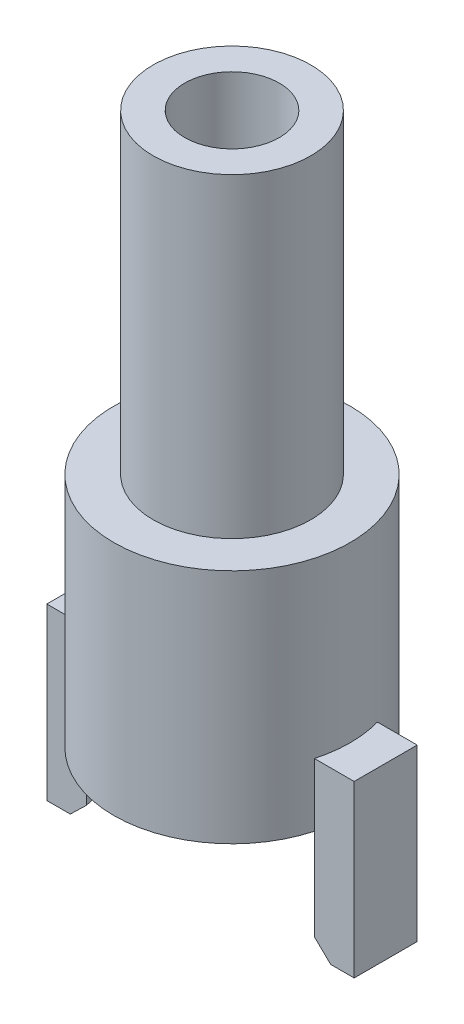
SolidWorks part; units mm, degrees
ref_plane "Front Plane" through (0, 0, 0) normal (0, 0, 1) x (1, 0, 0)
ref_plane "Top Plane" through (0, 0, 0) normal (0, 1, 0) x (1, 0, 0)
ref_plane "Right Plane" through (0, 0, 0) normal (1, 0, 0) x (0, 0, -1)
sketch "Hollow Cyl" plane through (0, 0, 0) normal (0, 1, 0) x (1, 0, 0)
  circle A0 centre (0, 0) radius 9.525
  circle A1 centre (0, 0) radius 7.62
  dimension "D1" = 19.05
  dimension "D2" = 15.24
sketch "Pin" plane through (0, 0, 0) normal (0, 1, 0) x (1, 0, 0)
  circle A0 centre (0, 0) radius 6.35
  circle A1 centre (0, 0) radius 3.81
  dimension "D1" = 12.7
  dimension "D2" = 7.62
extrude "Boss-Extrude4" add sketch "Pin" along normal blind 25.4
extrude "Boss-Extrude5" add sketch "Hollow Cyl" against normal blind 19.05 separate body
sketch "Sketch4" plane through (0, 0, 0) normal (0, 1, 0) x (1, 0, 0)
  circle A0 centre (0, 0) radius 7.62
  dimension "D1" = 15.24
extrude "Boss-Extrude7" add sketch "Sketch4" against normal blind 2.54
ref_plane "Plane1" through (0, -19.05, 0) normal (0, -1, 0) x (-1, 0, 0)
sketch "Sketch6" plane through (0, -19.05, 0) normal (0, -1, 0) x (-1, 0, 0)
  line L1 (12.3825, -2.54) -> (-12.3825, -2.54)
  line L2 (12.3825, -2.54) -> (12.3825, 2.54)
  line L3 (12.3825, 2.54) -> (-12.3825, 2.54)
  line L4 (-12.3825, -2.54) -> (-12.3825, 2.54)
  line L5 (12.3825, -2.54) -> (-12.3825, 2.54) construction
  line L6 (12.3825, 2.54) -> (-12.3825, -2.54) construction
  circle A0 centre (0, 0) radius 9.525 construction
  circle A1 centre (0, 0) radius 9.525
  circle A2 centre (0, 0) radius 9.525 construction
  circle A3 centre (0, 0) radius 9.525
  point P0 (0, 0)
  dimension "D1" = 24.765
  dimension "D2" = 5.08
extrude "Boss-Extrude9" add sketch "Sketch6" along normal blind 7.62 separate body contours A1 L1 L2 L3 | A1 L3 L4 L1 region at (-10.8949, -19.05, 0) region at (10.8949, -19.05, 0)
extrude "Boss-Extrude10" add sketch "Sketch6<5>" along normal blind 8.636 and the other way blind 5.08 contours A1 L1 L2 L3 | A1 L3 L4 L1 region at (-10.8949, -19.05, 0) region at (10.8949, -19.05, 0)
sketch "Sketch6<5>" plane through (0, -19.05, 0) normal (0, -1, 0) x (-1, 0, 0) same geometry as "Sketch6"
chamfer "Chamfer2" distance 1.27 angle 45 1 edges at (9.525, -27.686, 0)
chamfer "Chamfer4" distance 1.27 angle 45 1 edges at (-9.525, -27.686, 0)
